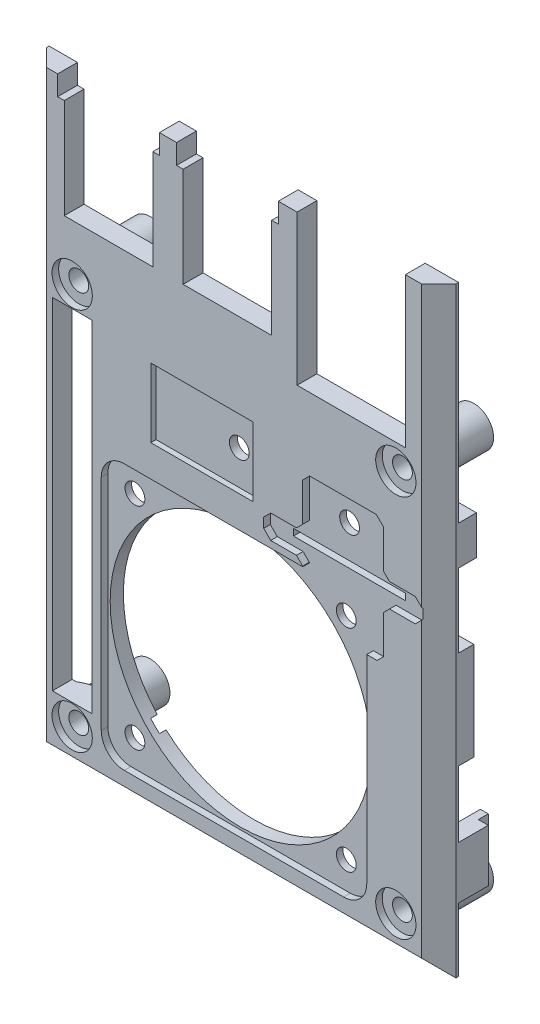
SolidWorks part; units mm, degrees
ref_plane "Front Plane" through (0, 0, 0) normal (0, 0, 1) x (1, 0, 0)
ref_plane "Top Plane" through (0, 0, 0) normal (0, 1, 0) x (1, 0, 0)
ref_plane "Right Plane" through (0, 0, 0) normal (1, 0, 0) x (0, 0, -1)
sketch "Sketch1" plane through (0, 0, 0) normal (0, 0, 1) x (1, 0, 0)
  line L0 (-28, 42.5) -> (28, -42.5) construction
  line L1 (-28, 42.5) -> (28, 42.5) construction
  line L2 (-28, 42.5) -> (-28, -42.5) construction
  line L3 (-28, -42.5) -> (28, -42.5) construction
  line L4 (28, 42.5) -> (28, -42.5) construction
  line L5 (0, 21.0664) -> (0, -30.1029) construction
  line L6 (-31, 45.5) -> (-26.7, 45.5)
  line L7 (-31, 45.5) -> (-31, -45.5)
  line L8 (-31, -45.5) -> (31, -45.5)
  line L9 (31, 45.5) -> (31, -45.5)
  line L10 (-31, 0) -> (31, 0) construction
  line L11 (-11.3, 45.5) -> (-8.7, 45.5)
  line L12 (-24.5, 19) -> (-24.5, -39) construction
  line L13 (-24.5, -39) -> (24.5, -39) construction
  line L14 (24.5, -39) -> (24.5, 19) construction
  line L15 (24.5, 19) -> (-24.5, 19) construction
  line L16 (8, 1.75) -> (25, 1.75)
  line L17 (8, 1.75) -> (8, 2.75)
  line L18 (8, 2.75) -> (25, 2.75)
  line L19 (25, 1.75) -> (25, 2.75)
  line L20 (6.7, 45.5) -> (9.55, 45.5)
  line L21 (-25.7, 42.5) -> (-25.7, 27.4)
  line L22 (-25.7, 27.4) -> (-12.3, 27.4)
  line L23 (-12.3, 42.5) -> (-12.3, 27.4)
  line L24 (25.95, 45.5) -> (31, 45.5)
  line L25 (-7.7, 42.5) -> (-7.7, 27.4)
  line L26 (-7.7, 27.4) -> (5.7, 27.4)
  line L27 (5.7, 42.5) -> (5.7, 27.4)
  line L29 (9.55, 45.5) -> (9.55, 22.8)
  line L30 (9.55, 22.8) -> (25.95, 22.8)
  line L31 (25.95, 45.5) -> (25.95, 22.8)
  line L40 (-27.5, 15.8) -> (-21.5, 15.8)
  line L41 (-11.3, 45.5) -> (-11.3, 42.5)
  line L42 (-11.3, 42.5) -> (-12.3, 42.5)
  line L43 (-27.5, 15.8) -> (-27.5, -35.8)
  line L44 (-7.7, 42.5) -> (-8.7, 42.5)
  line L45 (-8.7, 45.5) -> (-8.7, 42.5)
  line L46 (-25.7, 42.5) -> (-26.7, 42.5)
  line L47 (-26.7, 45.5) -> (-26.7, 42.5)
  line L48 (5.7, 42.5) -> (6.7, 42.5)
  line L49 (6.7, 45.5) -> (6.7, 42.5)
  line L50 (-27.5, -35.8) -> (-21.5, -35.8)
  line L51 (-21.5, 15.8) -> (-21.5, -35.8)
  circle A0 centre (24.5, -39) radius 1.5
  circle A1 centre (-24.5, -39) radius 1.5
  circle A2 centre (-24.5, 19) radius 1.5
  circle A3 centre (24.5, 19) radius 1.5
  point P4 (0, 0)
  point P11 (-24.5, -35.8)
  point P17 (25, 2.25)
  point P18 (16.5, 2.75)
  point P36 (17.75, 22.8)
  point P37 (-1, 27.4)
  point P38 (-19, 27.4)
  point P53 (0, -39)
  dimension "D24" = 3
  dimension "D1" = 56
  dimension "D2" = 85
  dimension "D3" = 62
  dimension "D4" = 91
  dimension "D5" = 10.25
  dimension "D6" = 29
  dimension "D7" = 47
  dimension "D8" = 19.7
  dimension "D9" = 16.4
  dimension "D10" = 15.1
  dimension "D11" = 13.4
  dimension "D13" = 0.5
  dimension "D14" = 17
  dimension "D15" = 1
  dimension "D16" = 3.2
  dimension "D19" = 44.75
  dimension "D20" = 11.5
  dimension "D21" = 58
  dimension "D22" = 49
  dimension "D23" = 3.5
  dimension "D26" = 3
  dimension "D27" = 1
  dimension "D29" = 3.2
extrude "Boss-Extrude1" add sketch "Sketch1" along normal blind 3
chamfer "Chamfer4" distance 2.6 angle 45 3 edges at (31, 0, 3) (0, -45.5, 3) (-31, 0, 3)
sketch "Sketch2" plane through (0, 0, 0) normal (0, 0, -1) x (-1, 0, 0)
  line L0 (0, 24.8559) -> (0, 9.4904) construction
  line L1 (-28.15, -42.5) -> (28.15, -42.5)
  line L2 (-28.15, -42.5) -> (-28.15, 17.7611)
  line L4 (28.15, -42.5) -> (28.15, 17.7611)
  line L5 (31, -45.5) -> (-31, -45.5) construction
  point P5 (0, -42.5)
  dimension "D1" = 56.3
  dimension "D2" = 3
sketch "Sketch3" plane through (0, 0, 0) normal (0, 0, -1) x (-1, 0, 0)
  line L0 (0, 35.5299) -> (0, -0.4089) construction
  line L1 (-28, 42.5) -> (28, -42.5) construction
  line L2 (-28, 42.5) -> (28, 42.5) construction
  line L3 (-28, 42.5) -> (-28, -42.5) construction
  line L4 (-28, -42.5) -> (28, -42.5) construction
  line L5 (28, 42.5) -> (28, -42.5) construction
  circle A0 centre (-24.5, 19) radius 3
  circle A1 centre (-24.5, 19) radius 1.5
  circle A2 centre (24.5, 19) radius 3
  circle A3 centre (24.5, 19) radius 1.5
  circle A4 centre (24.5, -39) radius 3
  circle A5 centre (24.5, -39) radius 1.5
  circle A6 centre (-24.5, -39) radius 3
  circle A7 centre (-24.5, -39) radius 1.5
  circle A8 centre (-24.5, 19) radius 1.5 construction
  point P7 (0, 0)
  dimension "D3" = 6
  dimension "D1" = 56
  dimension "D2" = 85
extrude "Boss-Extrude2" add sketch "Sketch3" along normal blind 8.8
sketch "Sketch4" plane through (0, 0, 3) normal (0, 0, 1) x (1, 0, 0)
  circle A0 centre (-24.5, 19) radius 3.05
  circle A1 centre (24.5, 19) radius 3.05
  circle A2 centre (24.5, -39) radius 3.05
  circle A3 centre (-24.5, -39) radius 3.05
  dimension "D1" = 6.1
extrude "Cut-Extrude1" cut sketch "Sketch4" against normal offset from surface (1 mm away) 2 up to face at (-21.5, -39, 0)
chamfer "Chamfer1" distance 1 angle 45 4 edges at (-21.5, -39, 0) (27.5, -39, 0) (27.5, 19, 0) (-21.5, 19, 0)
sketch "Sketch7" plane through (0, 0, 0) normal (0, 0, -1) x (-1, 0, 0)
  line L6 (-28.1, 45.5) -> (-31, 45.5)
  line L7 (-31, 45.5) -> (-31, -45.5)
  line L8 (-31, -45.5) -> (31, -45.5)
  line L9 (28.1, 45.5) -> (28.1, -42.6)
  line L10 (28.1, -42.6) -> (-28.1, -42.6)
  line L11 (-28.1, -42.6) -> (-28.1, 45.5)
  line L12 (28.1, 45.5) -> (28.1, -42.6)
  line L13 (28.1, -42.6) -> (-28.1, -42.6)
  line L14 (-28.1, -42.6) -> (-28.1, 45.5)
  line L15 (31, -45.5) -> (31, 45.5)
  line L16 (31, 45.5) -> (28.1, 45.5)
  dimension "D1" = 2.9
extrude "Cut-Extrude2" cut sketch "Sketch7" along normal up to next
sketch "Sketch5" plane through (0, 0, 0) normal (0, 0, -1) x (-1, 0, 0)
  line L0 (-31, -45.5) -> (-31, 45.5) construction
  line L1 (-31, 13.95) -> (-28.3, 13.95)
  line L2 (-31, 13.95) -> (-31, 8.05)
  line L3 (-31, 8.05) -> (-28.3, 8.05)
  line L4 (-28.3, 13.95) -> (-28.3, 8.05)
  line L5 (-28, 42.5) -> (28, -42.5) construction
  line L6 (-28, 42.5) -> (28, 42.5) construction
  line L7 (-28, 42.5) -> (-28, -42.5) construction
  line L8 (-28, -42.5) -> (28, -42.5) construction
  line L9 (28, 42.5) -> (28, -42.5) construction
  point P10 (0, 0)
  point P11 (-28.3, 11)
  dimension "D1" = 56
  dimension "D2" = 85
  dimension "D3" = 5.9
  dimension "D4" = 53.5
  dimension "D5" = 2.7
extrude "Boss-Extrude3" add sketch "Sketch5" along normal blind 2.7
sketch "Sketch6" plane through (0, 0, 0) normal (0, 0, -1) x (-1, 0, 0)
  line L0 (-31, -45.5) -> (-31, 8.05) construction
  line L1 (-31, -3.1) -> (-28.3, -3.1)
  line L2 (-31, -3.1) -> (-31, -17.9)
  line L3 (-31, -17.9) -> (-28.3, -17.9)
  line L4 (-28.3, -3.1) -> (-28.3, -17.9)
  line L5 (-28.3, 8.05) -> (-28.3, 13.95) construction
  line L6 (0, 42.5) -> (0, -42.5) construction
  line L7 (-28, 42.5) -> (28, 42.5) construction
  line L8 (-28, 42.5) -> (-28, -42.5) construction
  line L9 (-28, -42.5) -> (28, -42.5) construction
  line L10 (28, 42.5) -> (28, -42.5) construction
  point P14 (0, 0)
  point P15 (-31, -10.5)
  dimension "D1" = 14.8
  dimension "D2" = 56
  dimension "D3" = 85
  dimension "D4" = 32
extrude "Boss-Extrude4" add sketch "Sketch6" along normal blind 2.3
sketch "Sketch8" plane through (0, 0, 0) normal (0, 0, -1) x (-1, 0, 0)
  line L0 (0, -42.5) -> (0, 42.5) construction
  line L1 (-28, -42.5) -> (28, -42.5) construction
  line L2 (-28, -42.5) -> (-28, 42.5) construction
  line L3 (-28, 42.5) -> (28, 42.5) construction
  line L4 (28, -42.5) -> (28, 42.5) construction
  line L5 (-31, -45.5) -> (-31, -17.9) construction
  line L6 (-31, -27.925) -> (-28.3, -27.925)
  line L7 (-31, -27.925) -> (-31, -35.875)
  line L8 (-31, -35.875) -> (-28.3, -35.875)
  line L9 (-28.3, -27.925) -> (-28.3, -35.875)
  line L10 (-28.3, -17.9) -> (-28.3, -3.1) construction
  point P6 (0, 0)
  point P16 (-31, -31.9)
  dimension "D1" = 56
  dimension "D2" = 85
  dimension "D3" = 7.95
  dimension "D4" = 10.6
extrude "Boss-Extrude5" add sketch "Sketch8" along normal blind 6
sketch "Sketch10" plane through (31, 0, 0) normal (1, 0, 0) x (0, 0, -1)
  line L0 (6, -27.925) -> (0, -27.925) construction
  line L1 (4.5, -27.925) -> (6, -27.925)
  line L2 (4.5, -27.925) -> (4.5, -35.875)
  line L3 (4.5, -35.875) -> (6, -35.875)
  line L4 (6, -27.925) -> (6, -35.875)
  line L5 (4.5, -35.975) -> (4.5, -37.475) construction
extrude "Cut-Extrude4" cut sketch "Sketch10" against normal blind 1.5
sketch "Sketch15" plane through (0, 0, 3) normal (0, 0, 1) x (1, 0, 0)
  line L0 (0, 51.4024) -> (0, -16.4971) construction
  line L1 (-16, -4.6796) -> (16, -4.6796) construction
  line L2 (-16, -4.6796) -> (-16, -36.6796) construction
  line L3 (-16, -36.6796) -> (16, -36.6796) construction
  line L4 (16, -4.6796) -> (16, -36.6796) construction
  line L5 (-16, -20.6796) -> (0, -20.6796) construction
  circle A0 centre (-16, -4.6796) radius 1.5
  circle A1 centre (16, -4.6796) radius 1.5
  circle A2 centre (16, -36.6796) radius 1.5
  circle A3 centre (-16, -36.6796) radius 1.5
  circle A4 centre (-24.5, 19) radius 1.5 construction
  circle A5 centre (0, -20.6796) radius 19.75
  point P6 (0, -4.6796)
  dimension "D2" = 39.5
  dimension "D1" = 32
extrude "Cut-Extrude8" cut sketch "Sketch15" against normal up to next
sketch "Sketch16" plane through (0, 0, 3) normal (0, 0, 1) x (1, 0, 0)
  line L0 (-20.1, -0.5796) -> (20.1, -40.7796) construction
  line L1 (-16.6, -0.5796) -> (16.6, -0.5796)
  line L2 (-20.1, -4.0796) -> (-20.1, -37.2796)
  line L3 (-16.6, -40.7796) -> (16.6, -40.7796)
  line L4 (20.1, -4.0796) -> (20.1, -37.2796)
  circle A1 centre (0, -20.6796) radius 19.75 construction
  arc A2 (16.6, -0.5796) -> (20.1, -4.0796) centre (16.6, -4.0796) cw
  arc A3 (16.6, -40.7796) -> (20.1, -37.2796) centre (16.6, -37.2796) ccw
  arc A4 (-20.1, -37.2796) -> (-16.6, -40.7796) centre (-16.6, -37.2796) ccw
  arc A5 (-16.6, -0.5796) -> (-20.1, -4.0796) centre (-16.6, -4.0796) ccw
  point P4 (0, -20.6796)
  point P9 (20.1, -0.5796)
  dimension "D2" = 3.5
  dimension "D1" = 40.2
extrude "Cut-Extrude9" cut sketch "Sketch16" against normal blind 1
sketch "Sketch18" plane through (0, 0, 3) normal (0, 0, 1) x (1, 0, 0)
  line L0 (16.5, 7.75) -> (16.5, 2.75) construction
  line L1 (25, 2.75) -> (8, 2.75) construction
  circle A0 centre (16.5, 7.75) radius 1.5
  circle A1 centre (24.5, 19) radius 1.5 construction
  dimension "D1" = 5
extrude "Cut-Extrude11" cut sketch "Sketch18" against normal up to next
sketch "Sketch19" plane through (0, 0, 3) normal (0, 0, 1) x (1, 0, 0)
  line L0 (28.4, -42.9) -> (28.4, 45.5) construction
  line L1 (4.6, 2.95) -> (4.6, 1.55) construction
  line L2 (5.6, 3.95) -> (9.5, 3.95) construction
  line L3 (10.5, 4.95) -> (10.5, 10.75) construction
  line L4 (11.5, 11.75) -> (21.5, 11.75) construction
  line L5 (22.5, 10.75) -> (22.5, 4.95) construction
  line L6 (23.5, 3.95) -> (27.4, 3.95) construction
  line L7 (4.6, 2.25) -> (8, 2.25) construction
  line L8 (8, 2.75) -> (8, 1.75) construction
  line L9 (28.4, 2.95) -> (28.4, 1.55) construction
  line L10 (28.4, 2.25) -> (25, 2.25) construction
  line L11 (25, 1.75) -> (25, 2.75) construction
  line L12 (5.6, 3.95) -> (4.6, 2.95) construction
  line L13 (27.4, 3.95) -> (28.4, 2.95) construction
  line L14 (19.3, 7.75) -> (17.9, 10.1749) construction
  line L15 (22.6, -6.2914) -> (21.6586, -7.2328)
  line L16 (21.6586, -7.2328) -> (20.1, -7.2328)
  line L17 (17.9, 10.1749) -> (15.1, 10.1749) construction
  line L18 (15.1, 10.1749) -> (13.7, 7.75) construction
  line L19 (13.7, 7.75) -> (15.1, 5.3251) construction
  line L20 (15.1, 5.3251) -> (17.9, 5.3251) construction
  line L21 (17.9, 5.3251) -> (19.3, 7.75) construction
  line L22 (9.5, 3.95) -> (10.5, 4.95) construction
  line L23 (22.5, 4.95) -> (23.5, 3.95) construction
  line L24 (21.5, 11.75) -> (22.5, 10.75) construction
  line L25 (10.5, 10.75) -> (11.5, 11.75) construction
  line L26 (27.4, 0.55) -> (28.4, 1.55) construction
  line L27 (23.5, 0.55) -> (27.4, 0.55) construction
  line L28 (22.5, -0.45) -> (23.5, 0.55) construction
  line L29 (22.5, -6.25) -> (22.5, -0.45) construction
  line L31 (16.6, -0.5796) -> (-16.6, -0.5796) construction
  line L32 (25, 2.75) -> (8, 2.75) construction
  line L33 (10.5, -0.45) -> (10.5, -0.5796) construction
  line L34 (9.5, 0.55) -> (10.5, -0.45) construction
  line L35 (5.6, 0.55) -> (9.5, 0.55) construction
  line L36 (5.6, 0.55) -> (4.6, 1.55) construction
  line L37 (5.5586, 4.05) -> (9.4586, 4.05)
  line L38 (9.4586, 4.05) -> (10.4, 4.9914)
  line L39 (10.4, 4.9914) -> (10.4, 10.7914)
  line L40 (10.4, 10.7914) -> (11.4586, 11.85)
  line L41 (11.4586, 11.85) -> (21.5414, 11.85)
  line L42 (21.5414, 11.85) -> (22.6, 10.7914)
  line L43 (22.6, 10.7914) -> (22.6, 4.9914)
  line L44 (22.6, 4.9914) -> (23.5414, 4.05)
  line L45 (23.5414, 4.05) -> (27.4414, 4.05)
  line L46 (27.4414, 4.05) -> (28.5, 2.9914)
  line L47 (28.5, 2.9914) -> (28.5, 1.5086)
  line L48 (27.4414, 0.45) -> (28.5, 1.5086)
  line L49 (23.5414, 0.45) -> (27.4414, 0.45)
  line L50 (22.6, -0.4914) -> (23.5414, 0.45)
  line L51 (22.6, -6.2914) -> (22.6, -0.4914)
  line L55 (10.4, -0.4914) -> (10.4, -0.5796)
  line L56 (9.4586, 0.45) -> (10.4, -0.4914)
  line L57 (5.5586, 0.45) -> (9.4586, 0.45)
  line L58 (5.5586, 0.45) -> (4.5, 1.5086)
  line L59 (4.5, 2.9914) -> (4.5, 1.5086)
  line L60 (5.5586, 4.05) -> (4.5, 2.9914)
  line L61 (10.4, -0.5796) -> (16.6, -0.5796)
  line L64 (20.1, -4.0796) -> (20.1, -7.2328)
  line L66 (17.8905, -11.001) -> (22.6, -6.2914) construction
  line L67 (17.8402, -10.9098) -> (22.5, -6.25) construction
  line L68 (16.0267, -11.3217) -> (17.8402, -10.9098) construction
  line L69 (15.995, -11.4315) -> (17.8905, -11.001) construction
  line L70 (10.5, -5.795) -> (16.0267, -11.3217) construction
  line L71 (10.4, -5.8365) -> (15.995, -11.4315) construction
  line L72 (10.5, -0.45) -> (10.5, -5.795) construction
  line L73 (10.4, -0.4914) -> (10.4, -5.8365) construction
  arc A0 (20.1, -4.0796) -> (16.6, -0.5796) centre (16.6, -4.0796) ccw
  circle A2 centre (16.5, 7.75) radius 2.4249 construction
  point P1 (4.6, 3.95)
  point P4 (22.5, 3.95)
  point P5 (10.5, 3.95)
  point P6 (10.5, 11.75)
  point P7 (22.5, 11.75)
  point P9 (28.4, 3.95)
  dimension "D1" = 5.6
  dimension "D5" = 1.2
  dimension "D6" = 4
  dimension "D7" = 2.5
  dimension "D3" = 0.1
extrude "Cut-Extrude12" cut sketch "Sketch19" against normal up to surface (1 mm away) up to face at (14.5, -4.6796, 2)
sketch "Sketch20" plane through (0, 0, 3) normal (0, 0, 1) x (1, 0, 0)
  line L0 (10.4, -0.5796) -> (-16.6, -0.5796) construction
  line L1 (0, 9.4204) -> (0, 0) construction
  circle A0 centre (0, 9.4204) radius 1.5
  circle A1 centre (-24.5, 19) radius 1.5 construction
  dimension "D1" = 10
extrude "Cut-Extrude13" cut sketch "Sketch20" against normal up to next and the other way through all
sketch "Sketch21" plane through (0, 0, 3) normal (0, 0, 1) x (1, 0, 0)
  line L0 (0, 9.4204) -> (2.9, 9.4204) construction
  line L1 (-12.6, 14.6454) -> (2.9, 14.6454)
  line L2 (-12.6, 14.6454) -> (-12.6, 4.1954)
  line L3 (-12.6, 4.1954) -> (2.9, 4.1954)
  line L4 (2.9, 14.6454) -> (2.9, 4.1954)
  circle A1 centre (0, 9.4204) radius 1.5 construction
  point P6 (0, 0)
  point P8 (1.5, 9.4204)
  point P9 (0, 0)
  dimension "D1" = 15.5
  dimension "D2" = 10.45
  dimension "D3" = 2.9
extrude "Cut-Extrude14" cut sketch "Sketch21" against normal blind 0.8
sketch "Sketch17" plane through (0, 0, 0) normal (0, 0, -1) x (-1, 0, 0)
  circle A0 centre (-16.5, 7.75) radius 3.05
  circle A1 centre (-16, -4.6796) radius 3.05
  circle A2 centre (16, -4.6796) radius 3.05
  circle A3 centre (16, -36.6796) radius 3.05
  circle A4 centre (-16, -36.6796) radius 3.05
  circle A5 centre (-24.5, 19) radius 3.05 construction
  circle A6 centre (0, 9.4204) radius 3.05
extrude "Cut-Extrude10" cut sketch "Sketch17" against normal offset from surface (1 mm away) 1 up to face at (12.2445, -3.3852, 2)
